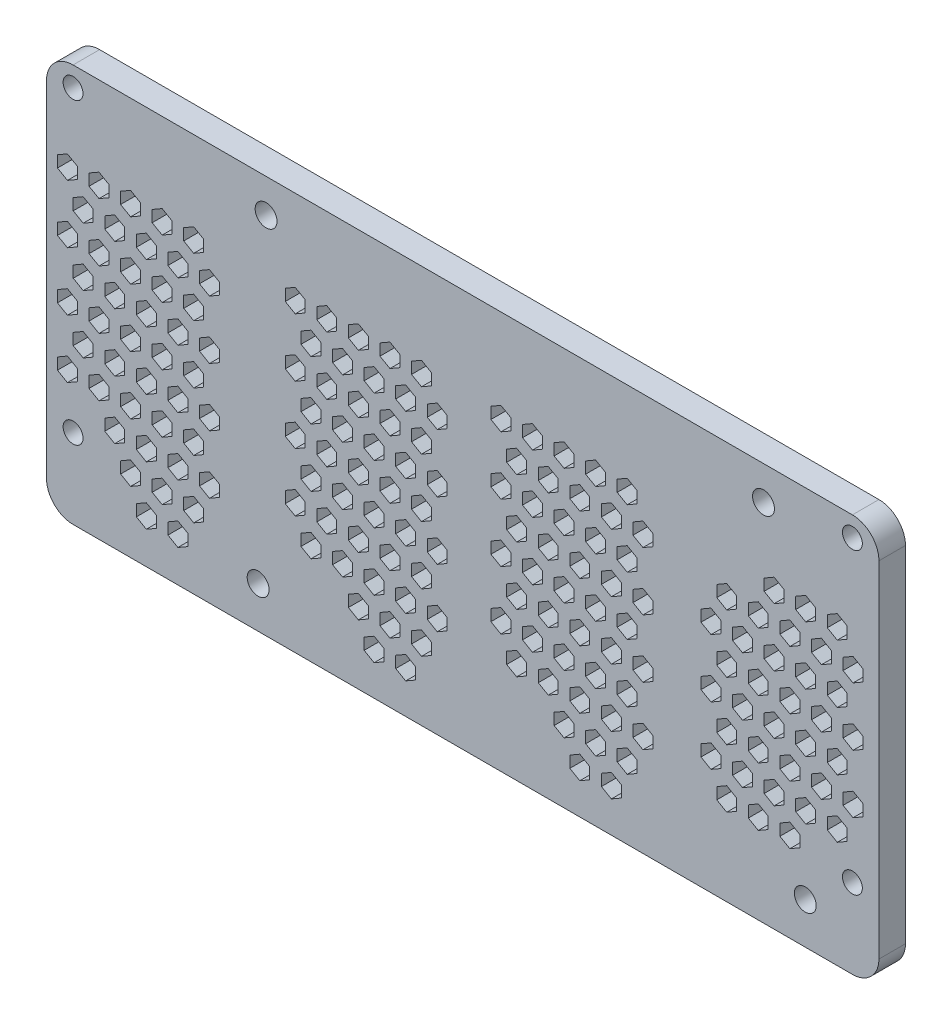
SolidWorks part; units mm, degrees
material "Acrylic (Medium-high impact)"
ref_plane "Front Plane" through (0, 0, 0) normal (0, 0, 1) x (1, 0, 0)
ref_plane "Top Plane" through (0, 0, 0) normal (0, 1, 0) x (1, 0, 0)
ref_plane "Right Plane" through (0, 0, 0) normal (1, 0, 0) x (0, 0, -1)
sketch "Sketch1" plane through (0, 0, 0) normal (0, 0, 1) x (1, 0, 0)
  line L1 (-44, 25.5882) -> (73.5, 25.5882)
  line L2 (-48, 21.5882) -> (-48, -30.4152)
  line L3 (-44, -34.4152) -> (73.5, -34.4152)
  line L4 (77.5, 21.5882) -> (77.5, -30.4152)
  line L10 (-44.8542, 13.5468) -> (-46.3542, 12.6808)
  line L11 (-46.3542, 12.6808) -> (-46.3542, 10.9488)
  line L12 (-46.3542, 10.9488) -> (-44.8542, 10.0827)
  line L13 (-44.8542, 10.0827) -> (-43.3542, 10.9488)
  line L14 (-43.3542, 10.9488) -> (-43.3542, 12.6808)
  line L15 (-43.3542, 12.6808) -> (-44.8542, 13.5468)
  line L17 (-42.4786, 9.1449) -> (-43.9786, 8.2789)
  line L18 (-43.9786, 8.2789) -> (-43.9786, 6.5468)
  line L19 (-43.9786, 6.5468) -> (-42.4786, 5.6808)
  line L20 (-42.4786, 5.6808) -> (-40.9786, 6.5468)
  line L21 (-40.9786, 6.5468) -> (-40.9786, 8.2789)
  line L22 (-40.9786, 8.2789) -> (-42.4786, 9.1449)
  line L23 (-40.0942, 13.5468) -> (-41.5942, 12.6808)
  line L24 (-41.5942, 12.6808) -> (-41.5942, 10.9488)
  line L25 (-41.5942, 10.9488) -> (-40.0942, 10.0827)
  line L26 (-40.0942, 10.0827) -> (-38.5942, 10.9488)
  line L27 (-38.5942, 10.9488) -> (-38.5942, 12.6808)
  line L28 (-38.5942, 12.6808) -> (-40.0942, 13.5468)
  line L29 (-37.7186, 9.1449) -> (-39.2186, 8.2789)
  line L30 (-39.2186, 8.2789) -> (-39.2186, 6.5468)
  line L31 (-39.2186, 6.5468) -> (-37.7186, 5.6808)
  line L32 (-37.7186, 5.6808) -> (-36.2186, 6.5468)
  line L33 (-36.2186, 6.5468) -> (-36.2186, 8.2789)
  line L34 (-36.2186, 8.2789) -> (-37.7186, 9.1449)
  line L35 (-35.3342, 13.5468) -> (-36.8342, 12.6808)
  line L36 (-36.8342, 12.6808) -> (-36.8342, 10.9488)
  line L37 (-36.8342, 10.9488) -> (-35.3342, 10.0827)
  line L38 (-35.3342, 10.0827) -> (-33.8342, 10.9488)
  line L39 (-33.8342, 10.9488) -> (-33.8342, 12.6808)
  line L40 (-33.8342, 12.6808) -> (-35.3342, 13.5468)
  line L41 (-32.9586, 9.1449) -> (-34.4586, 8.2789)
  line L42 (-34.4586, 8.2789) -> (-34.4586, 6.5468)
  line L43 (-34.4586, 6.5468) -> (-32.9586, 5.6808)
  line L44 (-32.9586, 5.6808) -> (-31.4586, 6.5468)
  line L45 (-31.4586, 6.5468) -> (-31.4586, 8.2789)
  line L46 (-31.4586, 8.2789) -> (-32.9586, 9.1449)
  line L47 (-30.5742, 13.5468) -> (-32.0742, 12.6808)
  line L48 (-32.0742, 12.6808) -> (-32.0742, 10.9488)
  line L49 (-32.0742, 10.9488) -> (-30.5742, 10.0827)
  line L50 (-30.5742, 10.0827) -> (-29.0742, 10.9488)
  line L51 (-29.0742, 10.9488) -> (-29.0742, 12.6808)
  line L52 (-29.0742, 12.6808) -> (-30.5742, 13.5468)
  line L53 (-28.1986, 9.1449) -> (-29.6986, 8.2789)
  line L54 (-29.6986, 8.2789) -> (-29.6986, 6.5468)
  line L55 (-29.6986, 6.5468) -> (-28.1986, 5.6808)
  line L56 (-28.1986, 5.6808) -> (-26.6986, 6.5468)
  line L57 (-26.6986, 6.5468) -> (-26.6986, 8.2789)
  line L58 (-26.6986, 8.2789) -> (-28.1986, 9.1449)
  line L59 (-25.8142, 13.5468) -> (-27.3142, 12.6808)
  line L60 (-27.3142, 12.6808) -> (-27.3142, 10.9488)
  line L61 (-27.3142, 10.9488) -> (-25.8142, 10.0827)
  line L62 (-25.8142, 10.0827) -> (-24.3142, 10.9488)
  line L63 (-24.3142, 10.9488) -> (-24.3142, 12.6808)
  line L64 (-24.3142, 12.6808) -> (-25.8142, 13.5468)
  line L65 (-23.4386, 9.1449) -> (-24.9386, 8.2789)
  line L66 (-24.9386, 8.2789) -> (-24.9386, 6.5468)
  line L67 (-24.9386, 6.5468) -> (-23.4386, 5.6808)
  line L68 (-23.4386, 5.6808) -> (-21.9386, 6.5468)
  line L69 (-21.9386, 6.5468) -> (-21.9386, 8.2789)
  line L70 (-21.9386, 8.2789) -> (-23.4386, 9.1449)
  line L71 (-40.0942, 4.7468) -> (-41.5942, 3.8808)
  line L72 (-41.5942, 3.8808) -> (-41.5942, 2.1488)
  line L73 (-41.5942, 2.1488) -> (-40.0942, 1.2827)
  line L74 (-40.0942, 1.2827) -> (-38.5942, 2.1488)
  line L75 (-38.5942, 2.1488) -> (-38.5942, 3.8808)
  line L76 (-38.5942, 3.8808) -> (-40.0942, 4.7468)
  line L77 (-37.7186, 0.3449) -> (-39.2186, -0.5211)
  line L78 (-39.2186, -0.5211) -> (-39.2186, -2.2532)
  line L79 (-39.2186, -2.2532) -> (-37.7186, -3.1192)
  line L80 (-37.7186, -3.1192) -> (-36.2186, -2.2532)
  line L81 (-36.2186, -2.2532) -> (-36.2186, -0.5211)
  line L82 (-36.2186, -0.5211) -> (-37.7186, 0.3449)
  line L83 (-35.3342, 4.7468) -> (-36.8342, 3.8808)
  line L84 (-36.8342, 3.8808) -> (-36.8342, 2.1488)
  line L85 (-36.8342, 2.1488) -> (-35.3342, 1.2827)
  line L86 (-35.3342, 1.2827) -> (-33.8342, 2.1488)
  line L87 (-33.8342, 2.1488) -> (-33.8342, 3.8808)
  line L88 (-33.8342, 3.8808) -> (-35.3342, 4.7468)
  line L89 (-32.9586, 0.3449) -> (-34.4586, -0.5211)
  line L90 (-34.4586, -0.5211) -> (-34.4586, -2.2532)
  line L91 (-34.4586, -2.2532) -> (-32.9586, -3.1192)
  line L92 (-32.9586, -3.1192) -> (-31.4586, -2.2532)
  line L93 (-31.4586, -2.2532) -> (-31.4586, -0.5211)
  line L94 (-31.4586, -0.5211) -> (-32.9586, 0.3449)
  line L95 (-30.5742, 4.7468) -> (-32.0742, 3.8808)
  line L96 (-32.0742, 3.8808) -> (-32.0742, 2.1488)
  line L97 (-32.0742, 2.1488) -> (-30.5742, 1.2827)
  line L98 (-30.5742, 1.2827) -> (-29.0742, 2.1488)
  line L99 (-29.0742, 2.1488) -> (-29.0742, 3.8808)
  line L100 (-29.0742, 3.8808) -> (-30.5742, 4.7468)
  line L101 (-28.1986, 0.3449) -> (-29.6986, -0.5211)
  line L102 (-29.6986, -0.5211) -> (-29.6986, -2.2532)
  line L103 (-29.6986, -2.2532) -> (-28.1986, -3.1192)
  line L104 (-28.1986, -3.1192) -> (-26.6986, -2.2532)
  line L105 (-26.6986, -2.2532) -> (-26.6986, -0.5211)
  line L106 (-26.6986, -0.5211) -> (-28.1986, 0.3449)
  line L107 (-25.8142, 4.7468) -> (-27.3142, 3.8808)
  line L108 (-27.3142, 3.8808) -> (-27.3142, 2.1488)
  line L109 (-27.3142, 2.1488) -> (-25.8142, 1.2827)
  line L110 (-25.8142, 1.2827) -> (-24.3142, 2.1488)
  line L111 (-24.3142, 2.1488) -> (-24.3142, 3.8808)
  line L112 (-24.3142, 3.8808) -> (-25.8142, 4.7468)
  line L113 (-23.4386, 0.3449) -> (-24.9386, -0.5211)
  line L114 (-24.9386, -0.5211) -> (-24.9386, -2.2532)
  line L115 (-24.9386, -2.2532) -> (-23.4386, -3.1192)
  line L116 (-23.4386, -3.1192) -> (-21.9386, -2.2532)
  line L117 (-21.9386, -2.2532) -> (-21.9386, -0.5211)
  line L118 (-21.9386, -0.5211) -> (-23.4386, 0.3449)
  line L119 (-40.0942, -4.0532) -> (-41.5942, -4.9192)
  line L120 (-41.5942, -4.9192) -> (-41.5942, -6.6512)
  line L121 (-41.5942, -6.6512) -> (-40.0942, -7.5173)
  line L122 (-40.0942, -7.5173) -> (-38.5942, -6.6512)
  line L123 (-38.5942, -6.6512) -> (-38.5942, -4.9192)
  line L124 (-38.5942, -4.9192) -> (-40.0942, -4.0532)
  line L125 (-37.7186, -8.4551) -> (-39.2186, -9.3211)
  line L126 (-39.2186, -9.3211) -> (-39.2186, -11.0532)
  line L127 (-39.2186, -11.0532) -> (-37.7186, -11.9192)
  line L128 (-37.7186, -11.9192) -> (-36.2186, -11.0532)
  line L129 (-36.2186, -11.0532) -> (-36.2186, -9.3211)
  line L130 (-36.2186, -9.3211) -> (-37.7186, -8.4551)
  line L131 (-35.3342, -4.0532) -> (-36.8342, -4.9192)
  line L132 (-36.8342, -4.9192) -> (-36.8342, -6.6512)
  line L133 (-36.8342, -6.6512) -> (-35.3342, -7.5173)
  line L134 (-35.3342, -7.5173) -> (-33.8342, -6.6512)
  line L135 (-33.8342, -6.6512) -> (-33.8342, -4.9192)
  line L136 (-33.8342, -4.9192) -> (-35.3342, -4.0532)
  line L137 (-32.9586, -8.4551) -> (-34.4586, -9.3211)
  line L138 (-34.4586, -9.3211) -> (-34.4586, -11.0532)
  line L139 (-34.4586, -11.0532) -> (-32.9586, -11.9192)
  line L140 (-32.9586, -11.9192) -> (-31.4586, -11.0532)
  line L141 (-31.4586, -11.0532) -> (-31.4586, -9.3211)
  line L142 (-31.4586, -9.3211) -> (-32.9586, -8.4551)
  line L143 (-30.5742, -4.0532) -> (-32.0742, -4.9192)
  line L144 (-32.0742, -4.9192) -> (-32.0742, -6.6512)
  line L145 (-32.0742, -6.6512) -> (-30.5742, -7.5173)
  line L146 (-30.5742, -7.5173) -> (-29.0742, -6.6512)
  line L147 (-29.0742, -6.6512) -> (-29.0742, -4.9192)
  line L148 (-29.0742, -4.9192) -> (-30.5742, -4.0532)
  line L149 (-28.1986, -8.4551) -> (-29.6986, -9.3211)
  line L150 (-29.6986, -9.3211) -> (-29.6986, -11.0532)
  line L151 (-29.6986, -11.0532) -> (-28.1986, -11.9192)
  line L152 (-28.1986, -11.9192) -> (-26.6986, -11.0532)
  line L153 (-26.6986, -11.0532) -> (-26.6986, -9.3211)
  line L154 (-26.6986, -9.3211) -> (-28.1986, -8.4551)
  line L155 (-25.8142, -4.0532) -> (-27.3142, -4.9192)
  line L156 (-27.3142, -4.9192) -> (-27.3142, -6.6512)
  line L157 (-27.3142, -6.6512) -> (-25.8142, -7.5173)
  line L158 (-25.8142, -7.5173) -> (-24.3142, -6.6512)
  line L159 (-24.3142, -6.6512) -> (-24.3142, -4.9192)
  line L160 (-24.3142, -4.9192) -> (-25.8142, -4.0532)
  line L161 (-23.4386, -8.4551) -> (-24.9386, -9.3211)
  line L162 (-24.9386, -9.3211) -> (-24.9386, -11.0532)
  line L163 (-24.9386, -11.0532) -> (-23.4386, -11.9192)
  line L164 (-23.4386, -11.9192) -> (-21.9386, -11.0532)
  line L165 (-21.9386, -11.0532) -> (-21.9386, -9.3211)
  line L166 (-21.9386, -9.3211) -> (-23.4386, -8.4551)
  line L167 (-40.0942, -12.8532) -> (-41.5942, -13.7192)
  line L168 (-41.5942, -13.7192) -> (-41.5942, -15.4512)
  line L169 (-41.5942, -15.4512) -> (-40.0942, -16.3173)
  line L170 (-40.0942, -16.3173) -> (-38.5942, -15.4512)
  line L171 (-38.5942, -15.4512) -> (-38.5942, -13.7192)
  line L172 (-38.5942, -13.7192) -> (-40.0942, -12.8532)
  line L173 (-37.7186, -17.2551) -> (-39.2186, -18.1211)
  line L174 (-39.2186, -18.1211) -> (-39.2186, -19.8532)
  line L175 (-39.2186, -19.8532) -> (-37.7186, -20.7192)
  line L176 (-37.7186, -20.7192) -> (-36.2186, -19.8532)
  line L177 (-36.2186, -19.8532) -> (-36.2186, -18.1211)
  line L178 (-36.2186, -18.1211) -> (-37.7186, -17.2551)
  line L179 (-35.3342, -12.8532) -> (-36.8342, -13.7192)
  line L180 (-36.8342, -13.7192) -> (-36.8342, -15.4512)
  line L181 (-36.8342, -15.4512) -> (-35.3342, -16.3173)
  line L182 (-35.3342, -16.3173) -> (-33.8342, -15.4512)
  line L183 (-33.8342, -15.4512) -> (-33.8342, -13.7192)
  line L184 (-33.8342, -13.7192) -> (-35.3342, -12.8532)
  line L185 (-32.9586, -17.2551) -> (-34.4586, -18.1211)
  line L186 (-34.4586, -18.1211) -> (-34.4586, -19.8532)
  line L187 (-34.4586, -19.8532) -> (-32.9586, -20.7192)
  line L188 (-32.9586, -20.7192) -> (-31.4586, -19.8532)
  line L189 (-31.4586, -19.8532) -> (-31.4586, -18.1211)
  line L190 (-31.4586, -18.1211) -> (-32.9586, -17.2551)
  line L191 (-30.5742, -12.8532) -> (-32.0742, -13.7192)
  line L192 (-32.0742, -13.7192) -> (-32.0742, -15.4512)
  line L193 (-32.0742, -15.4512) -> (-30.5742, -16.3173)
  line L194 (-30.5742, -16.3173) -> (-29.0742, -15.4512)
  line L195 (-29.0742, -15.4512) -> (-29.0742, -13.7192)
  line L196 (-29.0742, -13.7192) -> (-30.5742, -12.8532)
  line L197 (-28.1986, -17.2551) -> (-29.6986, -18.1211)
  line L198 (-29.6986, -18.1211) -> (-29.6986, -19.8532)
  line L199 (-29.6986, -19.8532) -> (-28.1986, -20.7192)
  line L200 (-28.1986, -20.7192) -> (-26.6986, -19.8532)
  line L201 (-26.6986, -19.8532) -> (-26.6986, -18.1211)
  line L202 (-26.6986, -18.1211) -> (-28.1986, -17.2551)
  line L203 (-25.8142, -12.8532) -> (-27.3142, -13.7192)
  line L204 (-27.3142, -13.7192) -> (-27.3142, -15.4512)
  line L205 (-27.3142, -15.4512) -> (-25.8142, -16.3173)
  line L206 (-25.8142, -16.3173) -> (-24.3142, -15.4512)
  line L207 (-24.3142, -15.4512) -> (-24.3142, -13.7192)
  line L208 (-24.3142, -13.7192) -> (-25.8142, -12.8532)
  line L209 (-23.4386, -17.2551) -> (-24.9386, -18.1211)
  line L210 (-24.9386, -18.1211) -> (-24.9386, -19.8532)
  line L211 (-24.9386, -19.8532) -> (-23.4386, -20.7192)
  line L212 (-23.4386, -20.7192) -> (-21.9386, -19.8532)
  line L213 (-21.9386, -19.8532) -> (-21.9386, -18.1211)
  line L214 (-21.9386, -18.1211) -> (-23.4386, -17.2551)
  line L227 (-35.3342, -21.6532) -> (-36.8342, -22.5192)
  line L228 (-36.8342, -22.5192) -> (-36.8342, -24.2512)
  line L229 (-36.8342, -24.2512) -> (-35.3342, -25.1173)
  line L230 (-35.3342, -25.1173) -> (-33.8342, -24.2512)
  line L231 (-33.8342, -24.2512) -> (-33.8342, -22.5192)
  line L232 (-33.8342, -22.5192) -> (-35.3342, -21.6532)
  line L233 (-32.9586, -26.0551) -> (-34.4586, -26.9211)
  line L234 (-34.4586, -26.9211) -> (-34.4586, -28.6532)
  line L235 (-34.4586, -28.6532) -> (-32.9586, -29.5192)
  line L236 (-32.9586, -29.5192) -> (-31.4586, -28.6532)
  line L237 (-31.4586, -28.6532) -> (-31.4586, -26.9211)
  line L238 (-31.4586, -26.9211) -> (-32.9586, -26.0551)
  line L239 (-30.5742, -21.6532) -> (-32.0742, -22.5192)
  line L240 (-32.0742, -22.5192) -> (-32.0742, -24.2512)
  line L241 (-32.0742, -24.2512) -> (-30.5742, -25.1173)
  line L242 (-30.5742, -25.1173) -> (-29.0742, -24.2512)
  line L243 (-29.0742, -24.2512) -> (-29.0742, -22.5192)
  line L244 (-29.0742, -22.5192) -> (-30.5742, -21.6532)
  line L245 (-28.1986, -26.0551) -> (-29.6986, -26.9211)
  line L246 (-29.6986, -26.9211) -> (-29.6986, -28.6532)
  line L247 (-29.6986, -28.6532) -> (-28.1986, -29.5192)
  line L248 (-28.1986, -29.5192) -> (-26.6986, -28.6532)
  line L249 (-26.6986, -28.6532) -> (-26.6986, -26.9211)
  line L250 (-26.6986, -26.9211) -> (-28.1986, -26.0551)
  line L251 (-25.8142, -21.6532) -> (-27.3142, -22.5192)
  line L252 (-27.3142, -22.5192) -> (-27.3142, -24.2512)
  line L253 (-27.3142, -24.2512) -> (-25.8142, -25.1173)
  line L254 (-25.8142, -25.1173) -> (-24.3142, -24.2512)
  line L255 (-24.3142, -24.2512) -> (-24.3142, -22.5192)
  line L256 (-24.3142, -22.5192) -> (-25.8142, -21.6532)
  line L263 (-44.8542, 4.7468) -> (-46.3542, 3.8808)
  line L264 (-46.3542, 3.8808) -> (-46.3542, 2.1488)
  line L265 (-46.3542, 2.1488) -> (-44.8542, 1.2827)
  line L266 (-44.8542, 1.2827) -> (-43.3542, 2.1488)
  line L267 (-43.3542, 2.1488) -> (-43.3542, 3.8808)
  line L268 (-43.3542, 3.8808) -> (-44.8542, 4.7468)
  line L269 (-42.4786, 0.3449) -> (-43.9786, -0.5211)
  line L270 (-43.9786, -0.5211) -> (-43.9786, -2.2532)
  line L271 (-43.9786, -2.2532) -> (-42.4786, -3.1192)
  line L272 (-42.4786, -3.1192) -> (-40.9786, -2.2532)
  line L273 (-40.9786, -2.2532) -> (-40.9786, -0.5211)
  line L274 (-40.9786, -0.5211) -> (-42.4786, 0.3449)
  line L275 (-44.8542, -4.0532) -> (-46.3542, -4.9192)
  line L276 (-46.3542, -4.9192) -> (-46.3542, -6.6512)
  line L277 (-46.3542, -6.6512) -> (-44.8542, -7.5173)
  line L278 (-44.8542, -7.5173) -> (-43.3542, -6.6512)
  line L279 (-43.3542, -6.6512) -> (-43.3542, -4.9192)
  line L280 (-43.3542, -4.9192) -> (-44.8542, -4.0532)
  line L281 (-42.4786, -8.4551) -> (-43.9786, -9.3211)
  line L282 (-43.9786, -9.3211) -> (-43.9786, -11.0532)
  line L283 (-43.9786, -11.0532) -> (-42.4786, -11.9192)
  line L284 (-42.4786, -11.9192) -> (-40.9786, -11.0532)
  line L285 (-40.9786, -11.0532) -> (-40.9786, -9.3211)
  line L286 (-40.9786, -9.3211) -> (-42.4786, -8.4551)
  line L287 (-44.8542, -12.8532) -> (-46.3542, -13.7192)
  line L288 (-46.3542, -13.7192) -> (-46.3542, -15.4512)
  line L289 (-46.3542, -15.4512) -> (-44.8542, -16.3173)
  line L290 (-44.8542, -16.3173) -> (-43.3542, -15.4512)
  line L291 (-43.3542, -15.4512) -> (-43.3542, -13.7192)
  line L292 (-43.3542, -13.7192) -> (-44.8542, -12.8532)
  line L311 (-44.8542, -21.6532) -> (-46.3542, -22.5192) [skipped]
  line L312 (-46.3542, -22.5192) -> (-46.3542, -24.2512) [skipped]
  line L313 (-46.3542, -24.2512) -> (-44.8542, -25.1173) [skipped]
  line L314 (-44.8542, -25.1173) -> (-43.3542, -24.2512) [skipped]
  line L315 (-43.3542, -24.2512) -> (-43.3542, -22.5192) [skipped]
  line L316 (-43.3542, -22.5192) -> (-44.8542, -21.6532) [skipped]
  line L317 (-42.4786, -26.0551) -> (-43.9786, -26.9211) [skipped]
  line L318 (-43.9786, -26.9211) -> (-43.9786, -28.6532) [skipped]
  line L319 (-43.9786, -28.6532) -> (-42.4786, -29.5192) [skipped]
  line L320 (-42.4786, -29.5192) -> (-40.9786, -28.6532) [skipped]
  line L321 (-40.9786, -28.6532) -> (-40.9786, -26.9211) [skipped]
  line L322 (-40.9786, -26.9211) -> (-42.4786, -26.0551) [skipped]
  line L323 (-37.7186, -26.0551) -> (-39.2186, -26.9211) [skipped]
  line L324 (-39.2186, -26.9211) -> (-39.2186, -28.6532) [skipped]
  line L325 (-39.2186, -28.6532) -> (-37.7186, -29.5192) [skipped]
  line L326 (-37.7186, -29.5192) -> (-36.2186, -28.6532) [skipped]
  line L327 (-36.2186, -28.6532) -> (-36.2186, -26.9211) [skipped]
  line L328 (-36.2186, -26.9211) -> (-37.7186, -26.0551) [skipped]
  line L329 (-40.0942, -21.6532) -> (-41.5942, -22.5192) [skipped]
  line L330 (-41.5942, -22.5192) -> (-41.5942, -24.2512) [skipped]
  line L331 (-41.5942, -24.2512) -> (-40.0942, -25.1173) [skipped]
  line L332 (-40.0942, -25.1173) -> (-38.5942, -24.2512) [skipped]
  line L333 (-38.5942, -24.2512) -> (-38.5942, -22.5192) [skipped]
  line L334 (-38.5942, -22.5192) -> (-40.0942, -21.6532) [skipped]
  line L335 (-23.4386, -26.0551) -> (-24.9386, -26.9211) [skipped]
  line L336 (-24.9386, -26.9211) -> (-24.9386, -28.6532) [skipped]
  line L337 (-24.9386, -28.6532) -> (-23.4386, -29.5192) [skipped]
  line L338 (-23.4386, -29.5192) -> (-21.9386, -28.6532) [skipped]
  line L339 (-21.9386, -28.6532) -> (-21.9386, -26.9211) [skipped]
  line L340 (-21.9386, -26.9211) -> (-23.4386, -26.0551) [skipped]
  line L347 (54.5534, 7.152) -> (53.0534, 6.286)
  line L348 (53.0534, 6.286) -> (53.0534, 4.554)
  line L349 (53.0534, 4.554) -> (54.5534, 3.6879)
  line L350 (54.5534, 3.6879) -> (56.0534, 4.554)
  line L351 (56.0534, 4.554) -> (56.0534, 6.286)
  line L352 (56.0534, 6.286) -> (54.5534, 7.152)
  line L359 (59.3134, 7.152) -> (57.8134, 6.286)
  line L360 (57.8134, 6.286) -> (57.8134, 4.554)
  line L361 (57.8134, 4.554) -> (59.3134, 3.6879)
  line L362 (59.3134, 3.6879) -> (60.8134, 4.554)
  line L363 (60.8134, 4.554) -> (60.8134, 6.286)
  line L364 (60.8134, 6.286) -> (59.3134, 7.152)
  line L365 (61.6978, 11.554) -> (60.1978, 10.6879)
  line L366 (60.1978, 10.6879) -> (60.1978, 8.9559)
  line L367 (60.1978, 8.9559) -> (61.6978, 8.0899)
  line L368 (61.6978, 8.0899) -> (63.1978, 8.9559)
  line L369 (63.1978, 8.9559) -> (63.1978, 10.6879)
  line L370 (63.1978, 10.6879) -> (61.6978, 11.554)
  line L371 (64.0734, 7.152) -> (62.5734, 6.286)
  line L372 (62.5734, 6.286) -> (62.5734, 4.554)
  line L373 (62.5734, 4.554) -> (64.0734, 3.6879)
  line L374 (64.0734, 3.6879) -> (65.5734, 4.554)
  line L375 (65.5734, 4.554) -> (65.5734, 6.286)
  line L376 (65.5734, 6.286) -> (64.0734, 7.152)
  line L377 (66.4578, 11.554) -> (64.9578, 10.6879)
  line L378 (64.9578, 10.6879) -> (64.9578, 8.9559)
  line L379 (64.9578, 8.9559) -> (66.4578, 8.0899)
  line L380 (66.4578, 8.0899) -> (67.9578, 8.9559)
  line L381 (67.9578, 8.9559) -> (67.9578, 10.6879)
  line L382 (67.9578, 10.6879) -> (66.4578, 11.554)
  line L383 (68.8334, 7.152) -> (67.3334, 6.286)
  line L384 (67.3334, 6.286) -> (67.3334, 4.554)
  line L385 (67.3334, 4.554) -> (68.8334, 3.6879)
  line L386 (68.8334, 3.6879) -> (70.3334, 4.554)
  line L387 (70.3334, 4.554) -> (70.3334, 6.286)
  line L388 (70.3334, 6.286) -> (68.8334, 7.152)
  line L389 (71.2178, 11.554) -> (69.7178, 10.6879)
  line L390 (69.7178, 10.6879) -> (69.7178, 8.9559)
  line L391 (69.7178, 8.9559) -> (71.2178, 8.0899)
  line L392 (71.2178, 8.0899) -> (72.7178, 8.9559)
  line L393 (72.7178, 8.9559) -> (72.7178, 10.6879)
  line L394 (72.7178, 10.6879) -> (71.2178, 11.554)
  line L395 (73.5934, 7.152) -> (72.0934, 6.286)
  line L396 (72.0934, 6.286) -> (72.0934, 4.554)
  line L397 (72.0934, 4.554) -> (73.5934, 3.6879)
  line L398 (73.5934, 3.6879) -> (75.0934, 4.554)
  line L399 (75.0934, 4.554) -> (75.0934, 6.286)
  line L400 (75.0934, 6.286) -> (73.5934, 7.152)
  line L401 (56.9378, 2.754) -> (55.4378, 1.8879)
  line L402 (55.4378, 1.8879) -> (55.4378, 0.1559)
  line L403 (55.4378, 0.1559) -> (56.9378, -0.7101)
  line L404 (56.9378, -0.7101) -> (58.4378, 0.1559)
  line L405 (58.4378, 0.1559) -> (58.4378, 1.8879)
  line L406 (58.4378, 1.8879) -> (56.9378, 2.754)
  line L407 (59.3134, -1.648) -> (57.8134, -2.514)
  line L408 (57.8134, -2.514) -> (57.8134, -4.246)
  line L409 (57.8134, -4.246) -> (59.3134, -5.1121)
  line L410 (59.3134, -5.1121) -> (60.8134, -4.246)
  line L411 (60.8134, -4.246) -> (60.8134, -2.514)
  line L412 (60.8134, -2.514) -> (59.3134, -1.648)
  line L413 (61.6978, 2.754) -> (60.1978, 1.8879)
  line L414 (60.1978, 1.8879) -> (60.1978, 0.1559)
  line L415 (60.1978, 0.1559) -> (61.6978, -0.7101)
  line L416 (61.6978, -0.7101) -> (63.1978, 0.1559)
  line L417 (63.1978, 0.1559) -> (63.1978, 1.8879)
  line L418 (63.1978, 1.8879) -> (61.6978, 2.754)
  line L419 (64.0734, -1.648) -> (62.5734, -2.514)
  line L420 (62.5734, -2.514) -> (62.5734, -4.246)
  line L421 (62.5734, -4.246) -> (64.0734, -5.1121)
  line L422 (64.0734, -5.1121) -> (65.5734, -4.246)
  line L423 (65.5734, -4.246) -> (65.5734, -2.514)
  line L424 (65.5734, -2.514) -> (64.0734, -1.648)
  line L425 (66.4578, 2.754) -> (64.9578, 1.8879)
  line L426 (64.9578, 1.8879) -> (64.9578, 0.1559)
  line L427 (64.9578, 0.1559) -> (66.4578, -0.7101)
  line L428 (66.4578, -0.7101) -> (67.9578, 0.1559)
  line L429 (67.9578, 0.1559) -> (67.9578, 1.8879)
  line L430 (67.9578, 1.8879) -> (66.4578, 2.754)
  line L431 (68.8334, -1.648) -> (67.3334, -2.514)
  line L432 (67.3334, -2.514) -> (67.3334, -4.246)
  line L433 (67.3334, -4.246) -> (68.8334, -5.1121)
  line L434 (68.8334, -5.1121) -> (70.3334, -4.246)
  line L435 (70.3334, -4.246) -> (70.3334, -2.514)
  line L436 (70.3334, -2.514) -> (68.8334, -1.648)
  line L437 (71.2178, 2.754) -> (69.7178, 1.8879)
  line L438 (69.7178, 1.8879) -> (69.7178, 0.1559)
  line L439 (69.7178, 0.1559) -> (71.2178, -0.7101)
  line L440 (71.2178, -0.7101) -> (72.7178, 0.1559)
  line L441 (72.7178, 0.1559) -> (72.7178, 1.8879)
  line L442 (72.7178, 1.8879) -> (71.2178, 2.754)
  line L443 (73.5934, -1.648) -> (72.0934, -2.514)
  line L444 (72.0934, -2.514) -> (72.0934, -4.246)
  line L445 (72.0934, -4.246) -> (73.5934, -5.1121)
  line L446 (73.5934, -5.1121) -> (75.0934, -4.246)
  line L447 (75.0934, -4.246) -> (75.0934, -2.514)
  line L448 (75.0934, -2.514) -> (73.5934, -1.648)
  line L449 (56.9378, -6.046) -> (55.4378, -6.9121)
  line L450 (55.4378, -6.9121) -> (55.4378, -8.6441)
  line L451 (55.4378, -8.6441) -> (56.9378, -9.5101)
  line L452 (56.9378, -9.5101) -> (58.4378, -8.6441)
  line L453 (58.4378, -8.6441) -> (58.4378, -6.9121)
  line L454 (58.4378, -6.9121) -> (56.9378, -6.046)
  line L455 (59.3134, -10.448) -> (57.8134, -11.314)
  line L456 (57.8134, -11.314) -> (57.8134, -13.046)
  line L457 (57.8134, -13.046) -> (59.3134, -13.9121)
  line L458 (59.3134, -13.9121) -> (60.8134, -13.046)
  line L459 (60.8134, -13.046) -> (60.8134, -11.314)
  line L460 (60.8134, -11.314) -> (59.3134, -10.448)
  line L461 (61.6978, -6.046) -> (60.1978, -6.9121)
  line L462 (60.1978, -6.9121) -> (60.1978, -8.6441)
  line L463 (60.1978, -8.6441) -> (61.6978, -9.5101)
  line L464 (61.6978, -9.5101) -> (63.1978, -8.6441)
  line L465 (63.1978, -8.6441) -> (63.1978, -6.9121)
  line L466 (63.1978, -6.9121) -> (61.6978, -6.046)
  line L467 (64.0734, -10.448) -> (62.5734, -11.314)
  line L468 (62.5734, -11.314) -> (62.5734, -13.046)
  line L469 (62.5734, -13.046) -> (64.0734, -13.9121)
  line L470 (64.0734, -13.9121) -> (65.5734, -13.046)
  line L471 (65.5734, -13.046) -> (65.5734, -11.314)
  line L472 (65.5734, -11.314) -> (64.0734, -10.448)
  line L473 (66.4578, -6.046) -> (64.9578, -6.9121)
  line L474 (64.9578, -6.9121) -> (64.9578, -8.6441)
  line L475 (64.9578, -8.6441) -> (66.4578, -9.5101)
  line L476 (66.4578, -9.5101) -> (67.9578, -8.6441)
  line L477 (67.9578, -8.6441) -> (67.9578, -6.9121)
  line L478 (67.9578, -6.9121) -> (66.4578, -6.046)
  line L479 (68.8334, -10.448) -> (67.3334, -11.314)
  line L480 (67.3334, -11.314) -> (67.3334, -13.046)
  line L481 (67.3334, -13.046) -> (68.8334, -13.9121)
  line L482 (68.8334, -13.9121) -> (70.3334, -13.046)
  line L483 (70.3334, -13.046) -> (70.3334, -11.314)
  line L484 (70.3334, -11.314) -> (68.8334, -10.448)
  line L485 (71.2178, -6.046) -> (69.7178, -6.9121)
  line L486 (69.7178, -6.9121) -> (69.7178, -8.6441)
  line L487 (69.7178, -8.6441) -> (71.2178, -9.5101)
  line L488 (71.2178, -9.5101) -> (72.7178, -8.6441)
  line L489 (72.7178, -8.6441) -> (72.7178, -6.9121)
  line L490 (72.7178, -6.9121) -> (71.2178, -6.046)
  line L491 (73.5934, -10.448) -> (72.0934, -11.314)
  line L492 (72.0934, -11.314) -> (72.0934, -13.046)
  line L493 (72.0934, -13.046) -> (73.5934, -13.9121)
  line L494 (73.5934, -13.9121) -> (75.0934, -13.046)
  line L495 (75.0934, -13.046) -> (75.0934, -11.314)
  line L496 (75.0934, -11.314) -> (73.5934, -10.448)
  line L497 (56.9378, -14.846) -> (55.4378, -15.7121)
  line L498 (55.4378, -15.7121) -> (55.4378, -17.4441)
  line L499 (55.4378, -17.4441) -> (56.9378, -18.3101)
  line L500 (56.9378, -18.3101) -> (58.4378, -17.4441)
  line L501 (58.4378, -17.4441) -> (58.4378, -15.7121)
  line L502 (58.4378, -15.7121) -> (56.9378, -14.846)
  line L503 (59.3134, -19.248) -> (57.8134, -20.114)
  line L504 (57.8134, -20.114) -> (57.8134, -21.846)
  line L505 (57.8134, -21.846) -> (59.3134, -22.7121)
  line L506 (59.3134, -22.7121) -> (60.8134, -21.846)
  line L507 (60.8134, -21.846) -> (60.8134, -20.114)
  line L508 (60.8134, -20.114) -> (59.3134, -19.248)
  line L509 (61.6978, -14.846) -> (60.1978, -15.7121)
  line L510 (60.1978, -15.7121) -> (60.1978, -17.4441)
  line L511 (60.1978, -17.4441) -> (61.6978, -18.3101)
  line L512 (61.6978, -18.3101) -> (63.1978, -17.4441)
  line L513 (63.1978, -17.4441) -> (63.1978, -15.7121)
  line L514 (63.1978, -15.7121) -> (61.6978, -14.846)
  line L515 (64.0734, -19.248) -> (62.5734, -20.114)
  line L516 (62.5734, -20.114) -> (62.5734, -21.846)
  line L517 (62.5734, -21.846) -> (64.0734, -22.7121)
  line L518 (64.0734, -22.7121) -> (65.5734, -21.846)
  line L519 (65.5734, -21.846) -> (65.5734, -20.114)
  line L520 (65.5734, -20.114) -> (64.0734, -19.248)
  line L521 (66.4578, -14.846) -> (64.9578, -15.7121)
  line L522 (64.9578, -15.7121) -> (64.9578, -17.4441)
  line L523 (64.9578, -17.4441) -> (66.4578, -18.3101)
  line L524 (66.4578, -18.3101) -> (67.9578, -17.4441)
  line L525 (67.9578, -17.4441) -> (67.9578, -15.7121)
  line L526 (67.9578, -15.7121) -> (66.4578, -14.846)
  line L533 (71.2178, -14.846) -> (69.7178, -15.7121)
  line L534 (69.7178, -15.7121) -> (69.7178, -17.4441)
  line L535 (69.7178, -17.4441) -> (71.2178, -18.3101)
  line L536 (71.2178, -18.3101) -> (72.7178, -17.4441)
  line L537 (72.7178, -17.4441) -> (72.7178, -15.7121)
  line L538 (72.7178, -15.7121) -> (71.2178, -14.846)
  line L575 (52.1778, 2.754) -> (50.6778, 1.8879)
  line L576 (50.6778, 1.8879) -> (50.6778, 0.1559)
  line L577 (50.6778, 0.1559) -> (52.1778, -0.7101)
  line L578 (52.1778, -0.7101) -> (53.6778, 0.1559)
  line L579 (53.6778, 0.1559) -> (53.6778, 1.8879)
  line L580 (53.6778, 1.8879) -> (52.1778, 2.754)
  line L581 (54.5534, -1.648) -> (53.0534, -2.514)
  line L582 (53.0534, -2.514) -> (53.0534, -4.246)
  line L583 (53.0534, -4.246) -> (54.5534, -5.1121)
  line L584 (54.5534, -5.1121) -> (56.0534, -4.246)
  line L585 (56.0534, -4.246) -> (56.0534, -2.514)
  line L586 (56.0534, -2.514) -> (54.5534, -1.648)
  line L587 (52.1778, -6.046) -> (50.6778, -6.9121)
  line L588 (50.6778, -6.9121) -> (50.6778, -8.6441)
  line L589 (50.6778, -8.6441) -> (52.1778, -9.5101)
  line L590 (52.1778, -9.5101) -> (53.6778, -8.6441)
  line L591 (53.6778, -8.6441) -> (53.6778, -6.9121)
  line L592 (53.6778, -6.9121) -> (52.1778, -6.046)
  line L593 (54.5534, -10.448) -> (53.0534, -11.314)
  line L594 (53.0534, -11.314) -> (53.0534, -13.046)
  line L595 (53.0534, -13.046) -> (54.5534, -13.9121)
  line L596 (54.5534, -13.9121) -> (56.0534, -13.046)
  line L597 (56.0534, -13.046) -> (56.0534, -11.314)
  line L598 (56.0534, -11.314) -> (54.5534, -10.448)
  line L599 (52.1778, -14.846) -> (50.6778, -15.7121)
  line L600 (50.6778, -15.7121) -> (50.6778, -17.4441)
  line L601 (50.6778, -17.4441) -> (52.1778, -18.3101)
  line L602 (52.1778, -18.3101) -> (53.6778, -17.4441)
  line L603 (53.6778, -17.4441) -> (53.6778, -15.7121)
  line L604 (53.6778, -15.7121) -> (52.1778, -14.846)
  line L605 (54.5534, -19.248) -> (53.0534, -20.114)
  line L606 (53.0534, -20.114) -> (53.0534, -21.846)
  line L607 (53.0534, -21.846) -> (54.5534, -22.7121)
  line L608 (54.5534, -22.7121) -> (56.0534, -21.846)
  line L609 (56.0534, -21.846) -> (56.0534, -20.114)
  line L610 (56.0534, -20.114) -> (54.5534, -19.248)
  line L611 (-10.5093, 13.2923) -> (-12.0093, 12.4263)
  line L612 (-12.0093, 12.4263) -> (-12.0093, 10.6942)
  line L613 (-12.0093, 10.6942) -> (-10.5093, 9.8282)
  line L614 (-10.5093, 9.8282) -> (-9.0093, 10.6942)
  line L615 (-9.0093, 10.6942) -> (-9.0093, 12.4263)
  line L616 (-9.0093, 12.4263) -> (-10.5093, 13.2923)
  line L617 (-8.1336, 8.8904) -> (-9.6336, 8.0244)
  line L618 (-9.6336, 8.0244) -> (-9.6336, 6.2923)
  line L619 (-9.6336, 6.2923) -> (-8.1336, 5.4263)
  line L620 (-8.1336, 5.4263) -> (-6.6336, 6.2923)
  line L621 (-6.6336, 6.2923) -> (-6.6336, 8.0244)
  line L622 (-6.6336, 8.0244) -> (-8.1336, 8.8904)
  line L623 (-5.7493, 13.2923) -> (-7.2493, 12.4263)
  line L624 (-7.2493, 12.4263) -> (-7.2493, 10.6942)
  line L625 (-7.2493, 10.6942) -> (-5.7493, 9.8282)
  line L626 (-5.7493, 9.8282) -> (-4.2493, 10.6942)
  line L627 (-4.2493, 10.6942) -> (-4.2493, 12.4263)
  line L628 (-4.2493, 12.4263) -> (-5.7493, 13.2923)
  line L629 (-3.3736, 8.8904) -> (-4.8736, 8.0244)
  line L630 (-4.8736, 8.0244) -> (-4.8736, 6.2923)
  line L631 (-4.8736, 6.2923) -> (-3.3736, 5.4263)
  line L632 (-3.3736, 5.4263) -> (-1.8736, 6.2923)
  line L633 (-1.8736, 6.2923) -> (-1.8736, 8.0244)
  line L634 (-1.8736, 8.0244) -> (-3.3736, 8.8904)
  line L635 (-0.9893, 13.2923) -> (-2.4893, 12.4263)
  line L636 (-2.4893, 12.4263) -> (-2.4893, 10.6942)
  line L637 (-2.4893, 10.6942) -> (-0.9893, 9.8282)
  line L638 (-0.9893, 9.8282) -> (0.5107, 10.6942)
  line L639 (0.5107, 10.6942) -> (0.5107, 12.4263)
  line L640 (0.5107, 12.4263) -> (-0.9893, 13.2923)
  line L641 (1.3864, 8.8904) -> (-0.1136, 8.0244)
  line L642 (-0.1136, 8.0244) -> (-0.1136, 6.2923)
  line L643 (-0.1136, 6.2923) -> (1.3864, 5.4263)
  line L644 (1.3864, 5.4263) -> (2.8864, 6.2923)
  line L645 (2.8864, 6.2923) -> (2.8864, 8.0244)
  line L646 (2.8864, 8.0244) -> (1.3864, 8.8904)
  line L647 (3.7707, 13.2923) -> (2.2707, 12.4263)
  line L648 (2.2707, 12.4263) -> (2.2707, 10.6942)
  line L649 (2.2707, 10.6942) -> (3.7707, 9.8282)
  line L650 (3.7707, 9.8282) -> (5.2707, 10.6942)
  line L651 (5.2707, 10.6942) -> (5.2707, 12.4263)
  line L652 (5.2707, 12.4263) -> (3.7707, 13.2923)
  line L653 (6.1464, 8.8904) -> (4.6464, 8.0244)
  line L654 (4.6464, 8.0244) -> (4.6464, 6.2923)
  line L655 (4.6464, 6.2923) -> (6.1464, 5.4263)
  line L656 (6.1464, 5.4263) -> (7.6464, 6.2923)
  line L657 (7.6464, 6.2923) -> (7.6464, 8.0244)
  line L658 (7.6464, 8.0244) -> (6.1464, 8.8904)
  line L659 (8.5307, 13.2923) -> (7.0307, 12.4263)
  line L660 (7.0307, 12.4263) -> (7.0307, 10.6942)
  line L661 (7.0307, 10.6942) -> (8.5307, 9.8282)
  line L662 (8.5307, 9.8282) -> (10.0307, 10.6942)
  line L663 (10.0307, 10.6942) -> (10.0307, 12.4263)
  line L664 (10.0307, 12.4263) -> (8.5307, 13.2923)
  line L665 (10.9064, 8.8904) -> (9.4064, 8.0244)
  line L666 (9.4064, 8.0244) -> (9.4064, 6.2923)
  line L667 (9.4064, 6.2923) -> (10.9064, 5.4263)
  line L668 (10.9064, 5.4263) -> (12.4064, 6.2923)
  line L669 (12.4064, 6.2923) -> (12.4064, 8.0244)
  line L670 (12.4064, 8.0244) -> (10.9064, 8.8904)
  line L671 (-5.7493, 4.4923) -> (-7.2493, 3.6263)
  line L672 (-7.2493, 3.6263) -> (-7.2493, 1.8942)
  line L673 (-7.2493, 1.8942) -> (-5.7493, 1.0282)
  line L674 (-5.7493, 1.0282) -> (-4.2493, 1.8942)
  line L675 (-4.2493, 1.8942) -> (-4.2493, 3.6263)
  line L676 (-4.2493, 3.6263) -> (-5.7493, 4.4923)
  line L677 (-3.3736, 0.0904) -> (-4.8736, -0.7756)
  line L678 (-4.8736, -0.7756) -> (-4.8736, -2.5077)
  line L679 (-4.8736, -2.5077) -> (-3.3736, -3.3737)
  line L680 (-3.3736, -3.3737) -> (-1.8736, -2.5077)
  line L681 (-1.8736, -2.5077) -> (-1.8736, -0.7756)
  line L682 (-1.8736, -0.7756) -> (-3.3736, 0.0904)
  line L683 (-0.9893, 4.4923) -> (-2.4893, 3.6263)
  line L684 (-2.4893, 3.6263) -> (-2.4893, 1.8942)
  line L685 (-2.4893, 1.8942) -> (-0.9893, 1.0282)
  line L686 (-0.9893, 1.0282) -> (0.5107, 1.8942)
  line L687 (0.5107, 1.8942) -> (0.5107, 3.6263)
  line L688 (0.5107, 3.6263) -> (-0.9893, 4.4923)
  line L689 (1.3864, 0.0904) -> (-0.1136, -0.7756)
  line L690 (-0.1136, -0.7756) -> (-0.1136, -2.5077)
  line L691 (-0.1136, -2.5077) -> (1.3864, -3.3737)
  line L692 (1.3864, -3.3737) -> (2.8864, -2.5077)
  line L693 (2.8864, -2.5077) -> (2.8864, -0.7756)
  line L694 (2.8864, -0.7756) -> (1.3864, 0.0904)
  line L695 (3.7707, 4.4923) -> (2.2707, 3.6263)
  line L696 (2.2707, 3.6263) -> (2.2707, 1.8942)
  line L697 (2.2707, 1.8942) -> (3.7707, 1.0282)
  line L698 (3.7707, 1.0282) -> (5.2707, 1.8942)
  line L699 (5.2707, 1.8942) -> (5.2707, 3.6263)
  line L700 (5.2707, 3.6263) -> (3.7707, 4.4923)
  line L701 (6.1464, 0.0904) -> (4.6464, -0.7756)
  line L702 (4.6464, -0.7756) -> (4.6464, -2.5077)
  line L703 (4.6464, -2.5077) -> (6.1464, -3.3737)
  line L704 (6.1464, -3.3737) -> (7.6464, -2.5077)
  line L705 (7.6464, -2.5077) -> (7.6464, -0.7756)
  line L706 (7.6464, -0.7756) -> (6.1464, 0.0904)
  line L707 (8.5307, 4.4923) -> (7.0307, 3.6263)
  line L708 (7.0307, 3.6263) -> (7.0307, 1.8942)
  line L709 (7.0307, 1.8942) -> (8.5307, 1.0282)
  line L710 (8.5307, 1.0282) -> (10.0307, 1.8942)
  line L711 (10.0307, 1.8942) -> (10.0307, 3.6263)
  line L712 (10.0307, 3.6263) -> (8.5307, 4.4923)
  line L713 (10.9064, 0.0904) -> (9.4064, -0.7756)
  line L714 (9.4064, -0.7756) -> (9.4064, -2.5077)
  line L715 (9.4064, -2.5077) -> (10.9064, -3.3737)
  line L716 (10.9064, -3.3737) -> (12.4064, -2.5077)
  line L717 (12.4064, -2.5077) -> (12.4064, -0.7756)
  line L718 (12.4064, -0.7756) -> (10.9064, 0.0904)
  line L719 (-5.7493, -4.3077) -> (-7.2493, -5.1737)
  line L720 (-7.2493, -5.1737) -> (-7.2493, -6.9058)
  line L721 (-7.2493, -6.9058) -> (-5.7493, -7.7718)
  line L722 (-5.7493, -7.7718) -> (-4.2493, -6.9058)
  line L723 (-4.2493, -6.9058) -> (-4.2493, -5.1737)
  line L724 (-4.2493, -5.1737) -> (-5.7493, -4.3077)
  line L725 (-3.3736, -8.7096) -> (-4.8736, -9.5756)
  line L726 (-4.8736, -9.5756) -> (-4.8736, -11.3077)
  line L727 (-4.8736, -11.3077) -> (-3.3736, -12.1737)
  line L728 (-3.3736, -12.1737) -> (-1.8736, -11.3077)
  line L729 (-1.8736, -11.3077) -> (-1.8736, -9.5756)
  line L730 (-1.8736, -9.5756) -> (-3.3736, -8.7096)
  line L731 (-0.9893, -4.3077) -> (-2.4893, -5.1737)
  line L732 (-2.4893, -5.1737) -> (-2.4893, -6.9058)
  line L733 (-2.4893, -6.9058) -> (-0.9893, -7.7718)
  line L734 (-0.9893, -7.7718) -> (0.5107, -6.9058)
  line L735 (0.5107, -6.9058) -> (0.5107, -5.1737)
  line L736 (0.5107, -5.1737) -> (-0.9893, -4.3077)
  line L737 (1.3864, -8.7096) -> (-0.1136, -9.5756)
  line L738 (-0.1136, -9.5756) -> (-0.1136, -11.3077)
  line L739 (-0.1136, -11.3077) -> (1.3864, -12.1737)
  line L740 (1.3864, -12.1737) -> (2.8864, -11.3077)
  line L741 (2.8864, -11.3077) -> (2.8864, -9.5756)
  line L742 (2.8864, -9.5756) -> (1.3864, -8.7096)
  line L743 (3.7707, -4.3077) -> (2.2707, -5.1737)
  line L744 (2.2707, -5.1737) -> (2.2707, -6.9058)
  line L745 (2.2707, -6.9058) -> (3.7707, -7.7718)
  line L746 (3.7707, -7.7718) -> (5.2707, -6.9058)
  line L747 (5.2707, -6.9058) -> (5.2707, -5.1737)
  line L748 (5.2707, -5.1737) -> (3.7707, -4.3077)
  line L749 (6.1464, -8.7096) -> (4.6464, -9.5756)
  line L750 (4.6464, -9.5756) -> (4.6464, -11.3077)
  line L751 (4.6464, -11.3077) -> (6.1464, -12.1737)
  line L752 (6.1464, -12.1737) -> (7.6464, -11.3077)
  line L753 (7.6464, -11.3077) -> (7.6464, -9.5756)
  line L754 (7.6464, -9.5756) -> (6.1464, -8.7096)
  line L755 (8.5307, -4.3077) -> (7.0307, -5.1737)
  line L756 (7.0307, -5.1737) -> (7.0307, -6.9058)
  line L757 (7.0307, -6.9058) -> (8.5307, -7.7718)
  line L758 (8.5307, -7.7718) -> (10.0307, -6.9058)
  line L759 (10.0307, -6.9058) -> (10.0307, -5.1737)
  line L760 (10.0307, -5.1737) -> (8.5307, -4.3077)
  line L761 (10.9064, -8.7096) -> (9.4064, -9.5756)
  line L762 (9.4064, -9.5756) -> (9.4064, -11.3077)
  line L763 (9.4064, -11.3077) -> (10.9064, -12.1737)
  line L764 (10.9064, -12.1737) -> (12.4064, -11.3077)
  line L765 (12.4064, -11.3077) -> (12.4064, -9.5756)
  line L766 (12.4064, -9.5756) -> (10.9064, -8.7096)
  line L767 (-5.7493, -13.1077) -> (-7.2493, -13.9737)
  line L768 (-7.2493, -13.9737) -> (-7.2493, -15.7058)
  line L769 (-7.2493, -15.7058) -> (-5.7493, -16.5718)
  line L770 (-5.7493, -16.5718) -> (-4.2493, -15.7058)
  line L771 (-4.2493, -15.7058) -> (-4.2493, -13.9737)
  line L772 (-4.2493, -13.9737) -> (-5.7493, -13.1077)
  line L773 (-3.3736, -17.5096) -> (-4.8736, -18.3756)
  line L774 (-4.8736, -18.3756) -> (-4.8736, -20.1077)
  line L775 (-4.8736, -20.1077) -> (-3.3736, -20.9737)
  line L776 (-3.3736, -20.9737) -> (-1.8736, -20.1077)
  line L777 (-1.8736, -20.1077) -> (-1.8736, -18.3756)
  line L778 (-1.8736, -18.3756) -> (-3.3736, -17.5096)
  line L779 (-0.9893, -13.1077) -> (-2.4893, -13.9737)
  line L780 (-2.4893, -13.9737) -> (-2.4893, -15.7058)
  line L781 (-2.4893, -15.7058) -> (-0.9893, -16.5718)
  line L782 (-0.9893, -16.5718) -> (0.5107, -15.7058)
  line L783 (0.5107, -15.7058) -> (0.5107, -13.9737)
  line L784 (0.5107, -13.9737) -> (-0.9893, -13.1077)
  line L785 (1.3864, -17.5096) -> (-0.1136, -18.3756)
  line L786 (-0.1136, -18.3756) -> (-0.1136, -20.1077)
  line L787 (-0.1136, -20.1077) -> (1.3864, -20.9737)
  line L788 (1.3864, -20.9737) -> (2.8864, -20.1077)
  line L789 (2.8864, -20.1077) -> (2.8864, -18.3756)
  line L790 (2.8864, -18.3756) -> (1.3864, -17.5096)
  line L791 (3.7707, -13.1077) -> (2.2707, -13.9737)
  line L792 (2.2707, -13.9737) -> (2.2707, -15.7058)
  line L793 (2.2707, -15.7058) -> (3.7707, -16.5718)
  line L794 (3.7707, -16.5718) -> (5.2707, -15.7058)
  line L795 (5.2707, -15.7058) -> (5.2707, -13.9737)
  line L796 (5.2707, -13.9737) -> (3.7707, -13.1077)
  line L797 (6.1464, -17.5096) -> (4.6464, -18.3756)
  line L798 (4.6464, -18.3756) -> (4.6464, -20.1077)
  line L799 (4.6464, -20.1077) -> (6.1464, -20.9737)
  line L800 (6.1464, -20.9737) -> (7.6464, -20.1077)
  line L801 (7.6464, -20.1077) -> (7.6464, -18.3756)
  line L802 (7.6464, -18.3756) -> (6.1464, -17.5096)
  line L803 (8.5307, -13.1077) -> (7.0307, -13.9737)
  line L804 (7.0307, -13.9737) -> (7.0307, -15.7058)
  line L805 (7.0307, -15.7058) -> (8.5307, -16.5718)
  line L806 (8.5307, -16.5718) -> (10.0307, -15.7058)
  line L807 (10.0307, -15.7058) -> (10.0307, -13.9737)
  line L808 (10.0307, -13.9737) -> (8.5307, -13.1077)
  line L809 (10.9064, -17.5096) -> (9.4064, -18.3756)
  line L810 (9.4064, -18.3756) -> (9.4064, -20.1077)
  line L811 (9.4064, -20.1077) -> (10.9064, -20.9737)
  line L812 (10.9064, -20.9737) -> (12.4064, -20.1077)
  line L813 (12.4064, -20.1077) -> (12.4064, -18.3756)
  line L814 (12.4064, -18.3756) -> (10.9064, -17.5096)
  line L815 (-0.9893, -21.9077) -> (-2.4893, -22.7737)
  line L816 (-2.4893, -22.7737) -> (-2.4893, -24.5058)
  line L817 (-2.4893, -24.5058) -> (-0.9893, -25.3718)
  line L818 (-0.9893, -25.3718) -> (0.5107, -24.5058)
  line L819 (0.5107, -24.5058) -> (0.5107, -22.7737)
  line L820 (0.5107, -22.7737) -> (-0.9893, -21.9077)
  line L821 (1.3864, -26.3096) -> (-0.1136, -27.1756)
  line L822 (-0.1136, -27.1756) -> (-0.1136, -28.9077)
  line L823 (-0.1136, -28.9077) -> (1.3864, -29.7737)
  line L824 (1.3864, -29.7737) -> (2.8864, -28.9077)
  line L825 (2.8864, -28.9077) -> (2.8864, -27.1756)
  line L826 (2.8864, -27.1756) -> (1.3864, -26.3096)
  line L827 (3.7707, -21.9077) -> (2.2707, -22.7737)
  line L828 (2.2707, -22.7737) -> (2.2707, -24.5058)
  line L829 (2.2707, -24.5058) -> (3.7707, -25.3718)
  line L830 (3.7707, -25.3718) -> (5.2707, -24.5058)
  line L831 (5.2707, -24.5058) -> (5.2707, -22.7737)
  line L832 (5.2707, -22.7737) -> (3.7707, -21.9077)
  line L833 (6.1464, -26.3096) -> (4.6464, -27.1756)
  line L834 (4.6464, -27.1756) -> (4.6464, -28.9077)
  line L835 (4.6464, -28.9077) -> (6.1464, -29.7737)
  line L836 (6.1464, -29.7737) -> (7.6464, -28.9077)
  line L837 (7.6464, -28.9077) -> (7.6464, -27.1756)
  line L838 (7.6464, -27.1756) -> (6.1464, -26.3096)
  line L839 (8.5307, -21.9077) -> (7.0307, -22.7737)
  line L840 (7.0307, -22.7737) -> (7.0307, -24.5058)
  line L841 (7.0307, -24.5058) -> (8.5307, -25.3718)
  line L842 (8.5307, -25.3718) -> (10.0307, -24.5058)
  line L843 (10.0307, -24.5058) -> (10.0307, -22.7737)
  line L844 (10.0307, -22.7737) -> (8.5307, -21.9077)
  line L845 (-10.5093, 4.4923) -> (-12.0093, 3.6263)
  line L846 (-12.0093, 3.6263) -> (-12.0093, 1.8942)
  line L847 (-12.0093, 1.8942) -> (-10.5093, 1.0282)
  line L848 (-10.5093, 1.0282) -> (-9.0093, 1.8942)
  line L849 (-9.0093, 1.8942) -> (-9.0093, 3.6263)
  line L850 (-9.0093, 3.6263) -> (-10.5093, 4.4923)
  line L851 (-8.1336, 0.0904) -> (-9.6336, -0.7756)
  line L852 (-9.6336, -0.7756) -> (-9.6336, -2.5077)
  line L853 (-9.6336, -2.5077) -> (-8.1336, -3.3737)
  line L854 (-8.1336, -3.3737) -> (-6.6336, -2.5077)
  line L855 (-6.6336, -2.5077) -> (-6.6336, -0.7756)
  line L856 (-6.6336, -0.7756) -> (-8.1336, 0.0904)
  line L857 (-10.5093, -4.3077) -> (-12.0093, -5.1737)
  line L858 (-12.0093, -5.1737) -> (-12.0093, -6.9058)
  line L859 (-12.0093, -6.9058) -> (-10.5093, -7.7718)
  line L860 (-10.5093, -7.7718) -> (-9.0093, -6.9058)
  line L861 (-9.0093, -6.9058) -> (-9.0093, -5.1737)
  line L862 (-9.0093, -5.1737) -> (-10.5093, -4.3077)
  line L863 (-8.1336, -8.7096) -> (-9.6336, -9.5756)
  line L864 (-9.6336, -9.5756) -> (-9.6336, -11.3077)
  line L865 (-9.6336, -11.3077) -> (-8.1336, -12.1737)
  line L866 (-8.1336, -12.1737) -> (-6.6336, -11.3077)
  line L867 (-6.6336, -11.3077) -> (-6.6336, -9.5756)
  line L868 (-6.6336, -9.5756) -> (-8.1336, -8.7096)
  line L869 (-10.5093, -13.1077) -> (-12.0093, -13.9737)
  line L870 (-12.0093, -13.9737) -> (-12.0093, -15.7058)
  line L871 (-12.0093, -15.7058) -> (-10.5093, -16.5718)
  line L872 (-10.5093, -16.5718) -> (-9.0093, -15.7058)
  line L873 (-9.0093, -15.7058) -> (-9.0093, -13.9737)
  line L874 (-9.0093, -13.9737) -> (-10.5093, -13.1077)
  line L875 (-8.1336, -17.5096) -> (-9.6336, -18.3756)
  line L876 (-9.6336, -18.3756) -> (-9.6336, -20.1077)
  line L877 (-9.6336, -20.1077) -> (-8.1336, -20.9737)
  line L878 (-8.1336, -20.9737) -> (-6.6336, -20.1077)
  line L879 (-6.6336, -20.1077) -> (-6.6336, -18.3756)
  line L880 (-6.6336, -18.3756) -> (-8.1336, -17.5096)
  line L881 (20.5044, 13.3912) -> (19.0044, 12.5251)
  line L882 (19.0044, 12.5251) -> (19.0044, 10.7931)
  line L883 (19.0044, 10.7931) -> (20.5044, 9.9271)
  line L884 (20.5044, 9.9271) -> (22.0044, 10.7931)
  line L885 (22.0044, 10.7931) -> (22.0044, 12.5251)
  line L886 (22.0044, 12.5251) -> (20.5044, 13.3912)
  line L887 (22.8801, 8.9892) -> (21.3801, 8.1232)
  line L888 (21.3801, 8.1232) -> (21.3801, 6.3912)
  line L889 (21.3801, 6.3912) -> (22.8801, 5.5251)
  line L890 (22.8801, 5.5251) -> (24.3801, 6.3912)
  line L891 (24.3801, 6.3912) -> (24.3801, 8.1232)
  line L892 (24.3801, 8.1232) -> (22.8801, 8.9892)
  line L893 (25.2644, 13.3912) -> (23.7644, 12.5251)
  line L894 (23.7644, 12.5251) -> (23.7644, 10.7931)
  line L895 (23.7644, 10.7931) -> (25.2644, 9.9271)
  line L896 (25.2644, 9.9271) -> (26.7644, 10.7931)
  line L897 (26.7644, 10.7931) -> (26.7644, 12.5251)
  line L898 (26.7644, 12.5251) -> (25.2644, 13.3912)
  line L899 (27.6401, 8.9892) -> (26.1401, 8.1232)
  line L900 (26.1401, 8.1232) -> (26.1401, 6.3912)
  line L901 (26.1401, 6.3912) -> (27.6401, 5.5251)
  line L902 (27.6401, 5.5251) -> (29.1401, 6.3912)
  line L903 (29.1401, 6.3912) -> (29.1401, 8.1232)
  line L904 (29.1401, 8.1232) -> (27.6401, 8.9892)
  line L905 (30.0244, 13.3912) -> (28.5244, 12.5251)
  line L906 (28.5244, 12.5251) -> (28.5244, 10.7931)
  line L907 (28.5244, 10.7931) -> (30.0244, 9.9271)
  line L908 (30.0244, 9.9271) -> (31.5244, 10.7931)
  line L909 (31.5244, 10.7931) -> (31.5244, 12.5251)
  line L910 (31.5244, 12.5251) -> (30.0244, 13.3912)
  line L911 (32.4001, 8.9892) -> (30.9001, 8.1232)
  line L912 (30.9001, 8.1232) -> (30.9001, 6.3912)
  line L913 (30.9001, 6.3912) -> (32.4001, 5.5251)
  line L914 (32.4001, 5.5251) -> (33.9001, 6.3912)
  line L915 (33.9001, 6.3912) -> (33.9001, 8.1232)
  line L916 (33.9001, 8.1232) -> (32.4001, 8.9892)
  line L917 (34.7844, 13.3912) -> (33.2844, 12.5251)
  line L918 (33.2844, 12.5251) -> (33.2844, 10.7931)
  line L919 (33.2844, 10.7931) -> (34.7844, 9.9271)
  line L920 (34.7844, 9.9271) -> (36.2844, 10.7931)
  line L921 (36.2844, 10.7931) -> (36.2844, 12.5251)
  line L922 (36.2844, 12.5251) -> (34.7844, 13.3912)
  line L923 (37.1601, 8.9892) -> (35.6601, 8.1232)
  line L924 (35.6601, 8.1232) -> (35.6601, 6.3912)
  line L925 (35.6601, 6.3912) -> (37.1601, 5.5251)
  line L926 (37.1601, 5.5251) -> (38.6601, 6.3912)
  line L927 (38.6601, 6.3912) -> (38.6601, 8.1232)
  line L928 (38.6601, 8.1232) -> (37.1601, 8.9892)
  line L929 (39.5444, 13.3912) -> (38.0444, 12.5251)
  line L930 (38.0444, 12.5251) -> (38.0444, 10.7931)
  line L931 (38.0444, 10.7931) -> (39.5444, 9.9271)
  line L932 (39.5444, 9.9271) -> (41.0444, 10.7931)
  line L933 (41.0444, 10.7931) -> (41.0444, 12.5251)
  line L934 (41.0444, 12.5251) -> (39.5444, 13.3912)
  line L935 (41.9201, 8.9892) -> (40.4201, 8.1232)
  line L936 (40.4201, 8.1232) -> (40.4201, 6.3912)
  line L937 (40.4201, 6.3912) -> (41.9201, 5.5251)
  line L938 (41.9201, 5.5251) -> (43.4201, 6.3912)
  line L939 (43.4201, 6.3912) -> (43.4201, 8.1232)
  line L940 (43.4201, 8.1232) -> (41.9201, 8.9892)
  line L941 (25.2644, 4.5912) -> (23.7644, 3.7251)
  line L942 (23.7644, 3.7251) -> (23.7644, 1.9931)
  line L943 (23.7644, 1.9931) -> (25.2644, 1.1271)
  line L944 (25.2644, 1.1271) -> (26.7644, 1.9931)
  line L945 (26.7644, 1.9931) -> (26.7644, 3.7251)
  line L946 (26.7644, 3.7251) -> (25.2644, 4.5912)
  line L947 (27.6401, 0.1892) -> (26.1401, -0.6768)
  line L948 (26.1401, -0.6768) -> (26.1401, -2.4088)
  line L949 (26.1401, -2.4088) -> (27.6401, -3.2749)
  line L950 (27.6401, -3.2749) -> (29.1401, -2.4088)
  line L951 (29.1401, -2.4088) -> (29.1401, -0.6768)
  line L952 (29.1401, -0.6768) -> (27.6401, 0.1892)
  line L953 (30.0244, 4.5912) -> (28.5244, 3.7251)
  line L954 (28.5244, 3.7251) -> (28.5244, 1.9931)
  line L955 (28.5244, 1.9931) -> (30.0244, 1.1271)
  line L956 (30.0244, 1.1271) -> (31.5244, 1.9931)
  line L957 (31.5244, 1.9931) -> (31.5244, 3.7251)
  line L958 (31.5244, 3.7251) -> (30.0244, 4.5912)
  line L959 (32.4001, 0.1892) -> (30.9001, -0.6768)
  line L960 (30.9001, -0.6768) -> (30.9001, -2.4088)
  line L961 (30.9001, -2.4088) -> (32.4001, -3.2749)
  line L962 (32.4001, -3.2749) -> (33.9001, -2.4088)
  line L963 (33.9001, -2.4088) -> (33.9001, -0.6768)
  line L964 (33.9001, -0.6768) -> (32.4001, 0.1892)
  line L965 (34.7844, 4.5912) -> (33.2844, 3.7251)
  line L966 (33.2844, 3.7251) -> (33.2844, 1.9931)
  line L967 (33.2844, 1.9931) -> (34.7844, 1.1271)
  line L968 (34.7844, 1.1271) -> (36.2844, 1.9931)
  line L969 (36.2844, 1.9931) -> (36.2844, 3.7251)
  line L970 (36.2844, 3.7251) -> (34.7844, 4.5912)
  line L971 (37.1601, 0.1892) -> (35.6601, -0.6768)
  line L972 (35.6601, -0.6768) -> (35.6601, -2.4088)
  line L973 (35.6601, -2.4088) -> (37.1601, -3.2749)
  line L974 (37.1601, -3.2749) -> (38.6601, -2.4088)
  line L975 (38.6601, -2.4088) -> (38.6601, -0.6768)
  line L976 (38.6601, -0.6768) -> (37.1601, 0.1892)
  line L977 (39.5444, 4.5912) -> (38.0444, 3.7251)
  line L978 (38.0444, 3.7251) -> (38.0444, 1.9931)
  line L979 (38.0444, 1.9931) -> (39.5444, 1.1271)
  line L980 (39.5444, 1.1271) -> (41.0444, 1.9931)
  line L981 (41.0444, 1.9931) -> (41.0444, 3.7251)
  line L982 (41.0444, 3.7251) -> (39.5444, 4.5912)
  line L983 (41.9201, 0.1892) -> (40.4201, -0.6768)
  line L984 (40.4201, -0.6768) -> (40.4201, -2.4088)
  line L985 (40.4201, -2.4088) -> (41.9201, -3.2749)
  line L986 (41.9201, -3.2749) -> (43.4201, -2.4088)
  line L987 (43.4201, -2.4088) -> (43.4201, -0.6768)
  line L988 (43.4201, -0.6768) -> (41.9201, 0.1892)
  line L989 (25.2644, -4.2088) -> (23.7644, -5.0749)
  line L990 (23.7644, -5.0749) -> (23.7644, -6.8069)
  line L991 (23.7644, -6.8069) -> (25.2644, -7.6729)
  line L992 (25.2644, -7.6729) -> (26.7644, -6.8069)
  line L993 (26.7644, -6.8069) -> (26.7644, -5.0749)
  line L994 (26.7644, -5.0749) -> (25.2644, -4.2088)
  line L995 (27.6401, -8.6108) -> (26.1401, -9.4768)
  line L996 (26.1401, -9.4768) -> (26.1401, -11.2088)
  line L997 (26.1401, -11.2088) -> (27.6401, -12.0749)
  line L998 (27.6401, -12.0749) -> (29.1401, -11.2088)
  line L999 (29.1401, -11.2088) -> (29.1401, -9.4768)
  line L1000 (29.1401, -9.4768) -> (27.6401, -8.6108)
  line L1001 (30.0244, -4.2088) -> (28.5244, -5.0749)
  line L1002 (28.5244, -5.0749) -> (28.5244, -6.8069)
  line L1003 (28.5244, -6.8069) -> (30.0244, -7.6729)
  line L1004 (30.0244, -7.6729) -> (31.5244, -6.8069)
  line L1005 (31.5244, -6.8069) -> (31.5244, -5.0749)
  line L1006 (31.5244, -5.0749) -> (30.0244, -4.2088)
  line L1007 (32.4001, -8.6108) -> (30.9001, -9.4768)
  line L1008 (30.9001, -9.4768) -> (30.9001, -11.2088)
  line L1009 (30.9001, -11.2088) -> (32.4001, -12.0749)
  line L1010 (32.4001, -12.0749) -> (33.9001, -11.2088)
  line L1011 (33.9001, -11.2088) -> (33.9001, -9.4768)
  line L1012 (33.9001, -9.4768) -> (32.4001, -8.6108)
  line L1013 (34.7844, -4.2088) -> (33.2844, -5.0749)
  line L1014 (33.2844, -5.0749) -> (33.2844, -6.8069)
  line L1015 (33.2844, -6.8069) -> (34.7844, -7.6729)
  line L1016 (34.7844, -7.6729) -> (36.2844, -6.8069)
  line L1017 (36.2844, -6.8069) -> (36.2844, -5.0749)
  line L1018 (36.2844, -5.0749) -> (34.7844, -4.2088)
  line L1019 (37.1601, -8.6108) -> (35.6601, -9.4768)
  line L1020 (35.6601, -9.4768) -> (35.6601, -11.2088)
  line L1021 (35.6601, -11.2088) -> (37.1601, -12.0749)
  line L1022 (37.1601, -12.0749) -> (38.6601, -11.2088)
  line L1023 (38.6601, -11.2088) -> (38.6601, -9.4768)
  line L1024 (38.6601, -9.4768) -> (37.1601, -8.6108)
  line L1025 (39.5444, -4.2088) -> (38.0444, -5.0749)
  line L1026 (38.0444, -5.0749) -> (38.0444, -6.8069)
  line L1027 (38.0444, -6.8069) -> (39.5444, -7.6729)
  line L1028 (39.5444, -7.6729) -> (41.0444, -6.8069)
  line L1029 (41.0444, -6.8069) -> (41.0444, -5.0749)
  line L1030 (41.0444, -5.0749) -> (39.5444, -4.2088)
  line L1031 (41.9201, -8.6108) -> (40.4201, -9.4768)
  line L1032 (40.4201, -9.4768) -> (40.4201, -11.2088)
  line L1033 (40.4201, -11.2088) -> (41.9201, -12.0749)
  line L1034 (41.9201, -12.0749) -> (43.4201, -11.2088)
  line L1035 (43.4201, -11.2088) -> (43.4201, -9.4768)
  line L1036 (43.4201, -9.4768) -> (41.9201, -8.6108)
  line L1037 (25.2644, -13.0088) -> (23.7644, -13.8749)
  line L1038 (23.7644, -13.8749) -> (23.7644, -15.6069)
  line L1039 (23.7644, -15.6069) -> (25.2644, -16.4729)
  line L1040 (25.2644, -16.4729) -> (26.7644, -15.6069)
  line L1041 (26.7644, -15.6069) -> (26.7644, -13.8749)
  line L1042 (26.7644, -13.8749) -> (25.2644, -13.0088)
  line L1043 (27.6401, -17.4108) -> (26.1401, -18.2768)
  line L1044 (26.1401, -18.2768) -> (26.1401, -20.0088)
  line L1045 (26.1401, -20.0088) -> (27.6401, -20.8749)
  line L1046 (27.6401, -20.8749) -> (29.1401, -20.0088)
  line L1047 (29.1401, -20.0088) -> (29.1401, -18.2768)
  line L1048 (29.1401, -18.2768) -> (27.6401, -17.4108)
  line L1049 (30.0244, -13.0088) -> (28.5244, -13.8749)
  line L1050 (28.5244, -13.8749) -> (28.5244, -15.6069)
  line L1051 (28.5244, -15.6069) -> (30.0244, -16.4729)
  line L1052 (30.0244, -16.4729) -> (31.5244, -15.6069)
  line L1053 (31.5244, -15.6069) -> (31.5244, -13.8749)
  line L1054 (31.5244, -13.8749) -> (30.0244, -13.0088)
  line L1055 (32.4001, -17.4108) -> (30.9001, -18.2768)
  line L1056 (30.9001, -18.2768) -> (30.9001, -20.0088)
  line L1057 (30.9001, -20.0088) -> (32.4001, -20.8749)
  line L1058 (32.4001, -20.8749) -> (33.9001, -20.0088)
  line L1059 (33.9001, -20.0088) -> (33.9001, -18.2768)
  line L1060 (33.9001, -18.2768) -> (32.4001, -17.4108)
  line L1061 (34.7844, -13.0088) -> (33.2844, -13.8749)
  line L1062 (33.2844, -13.8749) -> (33.2844, -15.6069)
  line L1063 (33.2844, -15.6069) -> (34.7844, -16.4729)
  line L1064 (34.7844, -16.4729) -> (36.2844, -15.6069)
  line L1065 (36.2844, -15.6069) -> (36.2844, -13.8749)
  line L1066 (36.2844, -13.8749) -> (34.7844, -13.0088)
  line L1067 (37.1601, -17.4108) -> (35.6601, -18.2768)
  line L1068 (35.6601, -18.2768) -> (35.6601, -20.0088)
  line L1069 (35.6601, -20.0088) -> (37.1601, -20.8749)
  line L1070 (37.1601, -20.8749) -> (38.6601, -20.0088)
  line L1071 (38.6601, -20.0088) -> (38.6601, -18.2768)
  line L1072 (38.6601, -18.2768) -> (37.1601, -17.4108)
  line L1073 (39.5444, -13.0088) -> (38.0444, -13.8749)
  line L1074 (38.0444, -13.8749) -> (38.0444, -15.6069)
  line L1075 (38.0444, -15.6069) -> (39.5444, -16.4729)
  line L1076 (39.5444, -16.4729) -> (41.0444, -15.6069)
  line L1077 (41.0444, -15.6069) -> (41.0444, -13.8749)
  line L1078 (41.0444, -13.8749) -> (39.5444, -13.0088)
  line L1079 (41.9201, -17.4108) -> (40.4201, -18.2768)
  line L1080 (40.4201, -18.2768) -> (40.4201, -20.0088)
  line L1081 (40.4201, -20.0088) -> (41.9201, -20.8749)
  line L1082 (41.9201, -20.8749) -> (43.4201, -20.0088)
  line L1083 (43.4201, -20.0088) -> (43.4201, -18.2768)
  line L1084 (43.4201, -18.2768) -> (41.9201, -17.4108)
  line L1085 (30.0244, -21.8088) -> (28.5244, -22.6749)
  line L1086 (28.5244, -22.6749) -> (28.5244, -24.4069)
  line L1087 (28.5244, -24.4069) -> (30.0244, -25.2729)
  line L1088 (30.0244, -25.2729) -> (31.5244, -24.4069)
  line L1089 (31.5244, -24.4069) -> (31.5244, -22.6749)
  line L1090 (31.5244, -22.6749) -> (30.0244, -21.8088)
  line L1091 (32.4001, -26.2108) -> (30.9001, -27.0768)
  line L1092 (30.9001, -27.0768) -> (30.9001, -28.8088)
  line L1093 (30.9001, -28.8088) -> (32.4001, -29.6749)
  line L1094 (32.4001, -29.6749) -> (33.9001, -28.8088)
  line L1095 (33.9001, -28.8088) -> (33.9001, -27.0768)
  line L1096 (33.9001, -27.0768) -> (32.4001, -26.2108)
  line L1097 (34.7844, -21.8088) -> (33.2844, -22.6749)
  line L1098 (33.2844, -22.6749) -> (33.2844, -24.4069)
  line L1099 (33.2844, -24.4069) -> (34.7844, -25.2729)
  line L1100 (34.7844, -25.2729) -> (36.2844, -24.4069)
  line L1101 (36.2844, -24.4069) -> (36.2844, -22.6749)
  line L1102 (36.2844, -22.6749) -> (34.7844, -21.8088)
  line L1103 (37.1601, -26.2108) -> (35.6601, -27.0768)
  line L1104 (35.6601, -27.0768) -> (35.6601, -28.8088)
  line L1105 (35.6601, -28.8088) -> (37.1601, -29.6749)
  line L1106 (37.1601, -29.6749) -> (38.6601, -28.8088)
  line L1107 (38.6601, -28.8088) -> (38.6601, -27.0768)
  line L1108 (38.6601, -27.0768) -> (37.1601, -26.2108)
  line L1109 (39.5444, -21.8088) -> (38.0444, -22.6749)
  line L1110 (38.0444, -22.6749) -> (38.0444, -24.4069)
  line L1111 (38.0444, -24.4069) -> (39.5444, -25.2729)
  line L1112 (39.5444, -25.2729) -> (41.0444, -24.4069)
  line L1113 (41.0444, -24.4069) -> (41.0444, -22.6749)
  line L1114 (41.0444, -22.6749) -> (39.5444, -21.8088)
  line L1115 (20.5044, 4.5912) -> (19.0044, 3.7251)
  line L1116 (19.0044, 3.7251) -> (19.0044, 1.9931)
  line L1117 (19.0044, 1.9931) -> (20.5044, 1.1271)
  line L1118 (20.5044, 1.1271) -> (22.0044, 1.9931)
  line L1119 (22.0044, 1.9931) -> (22.0044, 3.7251)
  line L1120 (22.0044, 3.7251) -> (20.5044, 4.5912)
  line L1121 (22.8801, 0.1892) -> (21.3801, -0.6768)
  line L1122 (21.3801, -0.6768) -> (21.3801, -2.4088)
  line L1123 (21.3801, -2.4088) -> (22.8801, -3.2749)
  line L1124 (22.8801, -3.2749) -> (24.3801, -2.4088)
  line L1125 (24.3801, -2.4088) -> (24.3801, -0.6768)
  line L1126 (24.3801, -0.6768) -> (22.8801, 0.1892)
  line L1127 (20.5044, -4.2088) -> (19.0044, -5.0749)
  line L1128 (19.0044, -5.0749) -> (19.0044, -6.8069)
  line L1129 (19.0044, -6.8069) -> (20.5044, -7.6729)
  line L1130 (20.5044, -7.6729) -> (22.0044, -6.8069)
  line L1131 (22.0044, -6.8069) -> (22.0044, -5.0749)
  line L1132 (22.0044, -5.0749) -> (20.5044, -4.2088)
  line L1133 (22.8801, -8.6108) -> (21.3801, -9.4768)
  line L1134 (21.3801, -9.4768) -> (21.3801, -11.2088)
  line L1135 (21.3801, -11.2088) -> (22.8801, -12.0749)
  line L1136 (22.8801, -12.0749) -> (24.3801, -11.2088)
  line L1137 (24.3801, -11.2088) -> (24.3801, -9.4768)
  line L1138 (24.3801, -9.4768) -> (22.8801, -8.6108)
  line L1139 (20.5044, -13.0088) -> (19.0044, -13.8749)
  line L1140 (19.0044, -13.8749) -> (19.0044, -15.6069)
  line L1141 (19.0044, -15.6069) -> (20.5044, -16.4729)
  line L1142 (20.5044, -16.4729) -> (22.0044, -15.6069)
  line L1143 (22.0044, -15.6069) -> (22.0044, -13.8749)
  line L1144 (22.0044, -13.8749) -> (20.5044, -13.0088)
  line L1145 (22.8801, -17.4108) -> (21.3801, -18.2768)
  line L1146 (21.3801, -18.2768) -> (21.3801, -20.0088)
  line L1147 (21.3801, -20.0088) -> (22.8801, -20.8749)
  line L1148 (22.8801, -20.8749) -> (24.3801, -20.0088)
  line L1149 (24.3801, -20.0088) -> (24.3801, -18.2768)
  line L1150 (24.3801, -18.2768) -> (22.8801, -17.4108)
  line L1151 (-42.4786, -17.2551) -> (-43.9786, -18.1211) [skipped]
  line L1152 (-43.9786, -18.1211) -> (-43.9786, -19.8532) [skipped]
  line L1153 (-43.9786, -19.8532) -> (-42.4786, -20.7192) [skipped]
  line L1154 (-42.4786, -20.7192) -> (-40.9786, -19.8532) [skipped]
  line L1155 (-40.9786, -19.8532) -> (-40.9786, -18.1211) [skipped]
  line L1156 (-40.9786, -18.1211) -> (-42.4786, -17.2551) [skipped]
  circle A0 centre (-44, 22.5882) radius 1.5
  circle A1 centre (73.5, 22.5882) radius 1.5
  circle A2 centre (-44, -22.4118) radius 1.5
  circle A3 centre (73.5, -22.4118) radius 1.5
  circle A4 centre (-14.9, 20.5148) radius 1.65
  circle A5 centre (-16.1, -28.1852) radius 1.65
  circle A6 centre (60.1, 20.5148) radius 1.65
  circle A7 centre (66.4, -28.1852) radius 1.65
  arc A8 (-44, 25.5882) -> (-48, 21.5882) centre (-44, 21.5882) ccw
  circle A9 centre (-44.8542, 11.8148) radius 1.5 construction
  circle A10 centre (-42.4786, 7.4129) radius 1.5 construction
  arc A11 (-44, -34.4152) -> (-48, -30.4152) centre (-44, -30.4152) cw
  arc A12 (77.5, -30.4152) -> (73.5, -34.4152) centre (73.5, -30.4152) cw
  arc A13 (77.5, 21.5882) -> (73.5, 25.5882) centre (73.5, 21.5882) ccw
  point P14 (-48, -34.4152)
  point P26 (-48, 25.5882)
  point P244 (77.5, 25.5882)
  dimension "D4" = 3
  dimension "D5" = 3
  dimension "D8" = 3
  dimension "D13" = 3
  dimension "D14" = 4
  dimension "D15" = 48.7
  dimension "D18" = 75
  dimension "D19" = 54.93
  dimension "D20" = 3.3
  dimension "D21" = 3.3
  dimension "D22" = 3.3
  dimension "D23" = 3.3
  dimension "D24" = 4
  dimension "D9" = 4
  dimension "D10" = 4
  dimension "D1" = 125.5
  dimension "D3" = 117.5
  dimension "D6" = 4
  dimension "D7" = 4
  dimension "D11" = 3
  dimension "D12" = 45
  dimension "D16" = 48
  dimension "D17" = 5.0734
  dimension "D25" = 2
  dimension "D26" = 3
  dimension "D27" = 3
  dimension "D28" = 7
  dimension "D29" = 0.8756
  dimension "D30" = 1.8038
  dimension "D31" = 0.8756
  dimension "D34" = 6.23
  dimension "D35" = 6.23
  dimension "D36" = 45
  dimension "D37" = 3
  dimension "D38" = 45
  dimension "D40" = 31.9
  dimension "D41" = 11.1
  dimension "D32" = 5
  dimension "D33" = 5
extrude "Boss-Extrude5" add sketch "Sketch1" along normal blind 4
